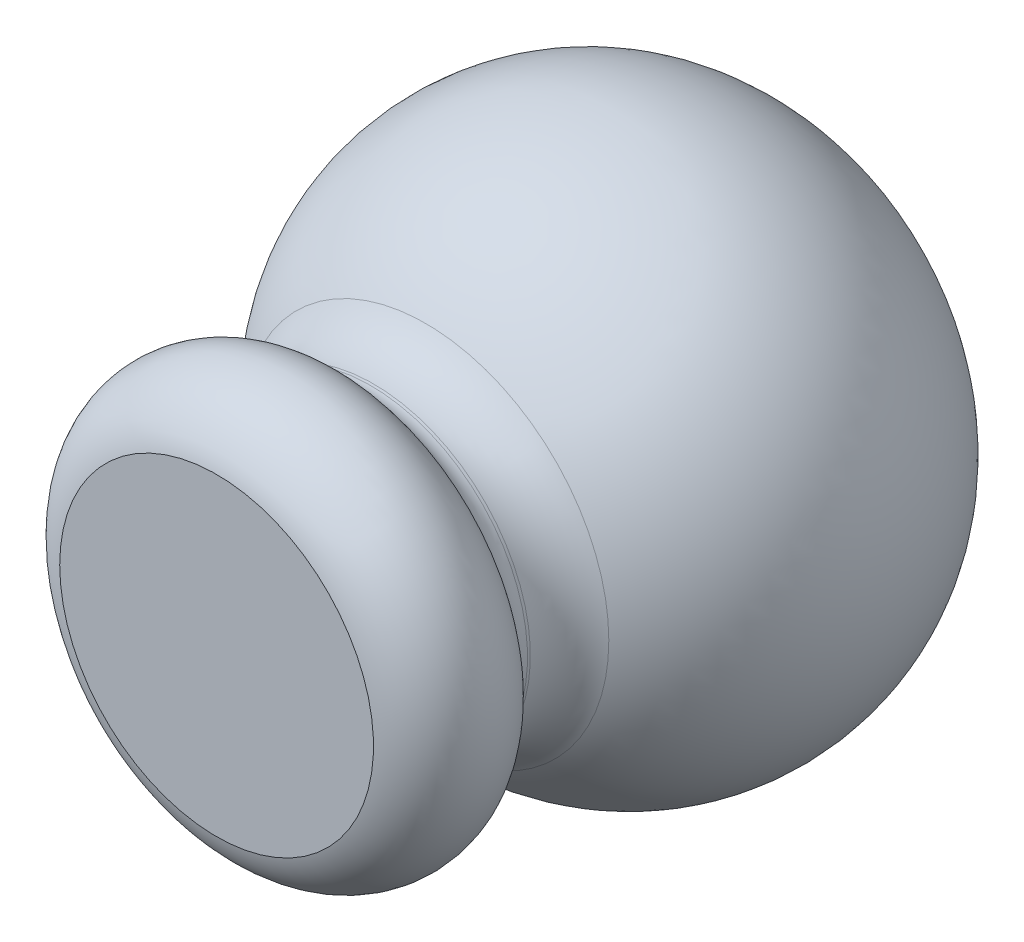
SolidWorks part; units mm, degrees
material "Латунь"
ref_plane "Front" through (0, 0, 0) normal (0, 0, 1) x (1, 0, 0)
ref_plane "Top" through (0, 0, 0) normal (0, 1, 0) x (1, 0, 0)
ref_plane "Right" through (0, 0, 0) normal (1, 0, 0) x (0, 0, -1)
ref_axis "Ось1" through (0, 0, 50) along (0, 0, -1)
sketch "Эскиз1" plane through (0, 0, 0) normal (0, 1, 0) x (1, 0, 0)
  line L12 (-3, -8) -> (-3, -8.0544)
  line L13 (-3, -11) -> (0, -11)
  line L14 (0, 0) -> (0, -19.4089) construction
  line L15 (-3.5, 0) -> (-1.2, 0)
  line L16 (-1.2, 0) -> (-1.2, -7)
  line L17 (-1.2, -7) -> (0, -7)
  line L18 (-3.5, -12.4392) -> (-3.5, 0) construction
  line L19 (0, -7) -> (0, -11)
  arc A0 (-3.5, 0) -> (-3.5, -7) centre (-0.875, -3.5) ccw
  arc A1 (-3.5, -7) -> (-3, -8) centre (-4.25, -8) cw
  arc A2 (-3, -8.0544) -> (-3.2732, -8.5) centre (-3.5, -8.0544) cw
  arc A3 (-3.2732, -8.5) -> (-3, -11) centre (-2.6634, -9.6983) ccw
  point P26 (-5.25, -3.5)
  point P27 (-4, -9.8444)
  dimension "D2" = 1.75
  dimension "D3" = 11
  dimension "D4" = 7
  dimension "D5" = 2.4
  dimension "D6" = 0.5
  dimension "D7" = 10.5
  dimension "D9" = 7
  dimension "D11" = 6
  dimension "D12" = 7
  dimension "D14" = 2.5
revolve "Повернуть2" add sketch "Эскиз1" angle 360 about L14
